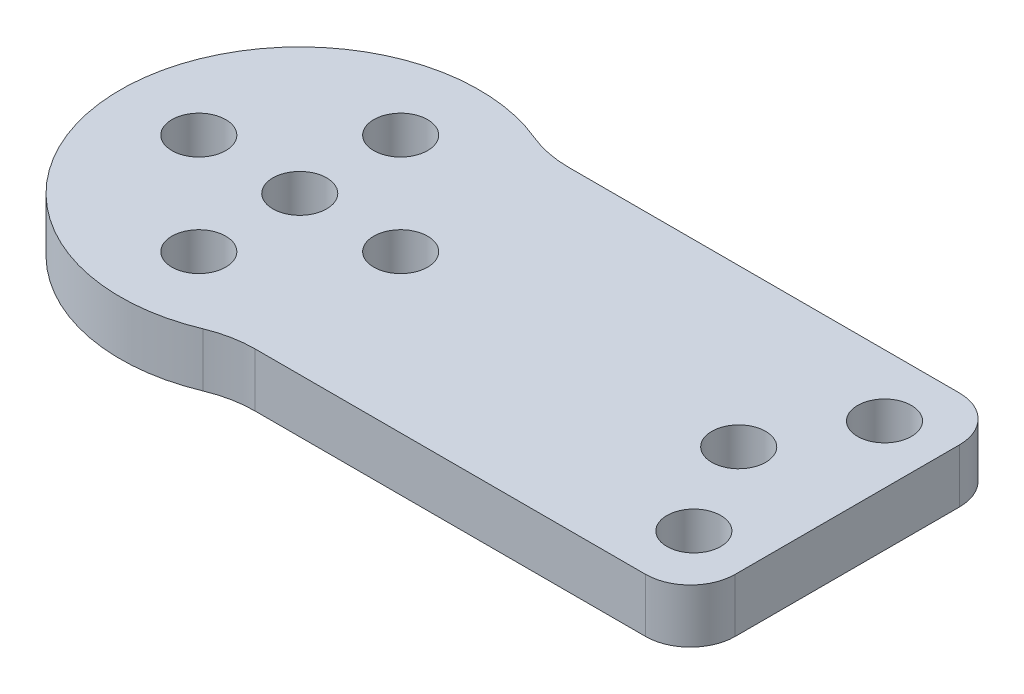
SolidWorks part; units mm, degrees
ref_plane "Front Plane" through (0, 0, 0) normal (0, 0, 1) x (1, 0, 0)
ref_plane "Top Plane" through (0, 0, 0) normal (0, 1, 0) x (1, 0, 0)
ref_plane "Right Plane" through (0, 0, 0) normal (1, 0, 0) x (0, 0, -1)
sketch "Sketch1" plane through (0, 0, 0) normal (0, 1, 0) x (1, 0, 0)
  line L0 (-12.7, 0) -> (12.7, 0) construction
  line L1 (-12.7, -7) -> (12.7, -7) construction
  line L2 (-12.7, 7) -> (12.7, 7) construction
  line L3 (11.7164, 7) -> (-8.827, 7)
  line L4 (-8.827, -7) -> (11.7164, -7)
  line L5 (11.7164, -7) -> (11.7164, 7)
  arc A0 (-8.827, 7) -> (-8.827, -7) centre (-12.7, 0) ccw
  circle A1 centre (-12.7, 0) radius 25.4 construction
  point P3 (0, 0)
  dimension "D1" = 50.8
  dimension "D2" = 16
  dimension "D3" = 7
  dimension "D4" = 7
extrude "Boss-Extrude1" add sketch "Sketch1" along normal mid plane 2.4
fillet "Fillet1" radius 2 2 edges at (11.7164, 0, -7) (11.7164, 0, 7)
fillet "Fillet2" radius 5 2 edges at (-8.827, 0, -7) (-8.827, 0, 7)
sketch "Sketch2" plane through (0, 1.2, 0) normal (0, 1, 0) x (1, 0, 0)
  circle A0 centre (-12.7, 0) radius 4.5 construction
  circle A1 centre (-8.2, 0) radius 1.2
  circle A2 centre (-12.7, 4.5) radius 1.2
  circle A3 centre (-17.2, 0) radius 1.2
  circle A4 centre (-12.7, -4.5) radius 1.2
  circle A5 centre (-12.7, 0) radius 1.2
  dimension "D1" = 2.4
  dimension "D2" = 9
extrude "Cut-Extrude1" cut sketch "Sketch2" against normal through all
sketch "Sketch3" plane through (0, 1.2, 0) normal (0, 1, 0) x (1, 0, 0)
  line L0 (9.1214, 4.25) -> (9.1214, -4.25) construction
  line L1 (9.1214, -4.25) -> (6.8714, 0) construction
  line L2 (6.8714, 0) -> (9.1214, 4.25) construction
  line L3 (11.7164, -5) -> (11.7164, 5) construction
  circle A0 centre (9.1214, 4.25) radius 1.2
  circle A1 centre (9.1214, -4.25) radius 1.2
  circle A2 centre (6.8714, 0) radius 1.2
  point P6 (0, 0)
  dimension "D1" = 2.4
  dimension "D2" = 2.25
  dimension "D3" = 4.25
  dimension "D4" = 2.595
extrude "Cut-Extrude2" cut sketch "Sketch3" against normal through all
equation "\"D4@Sketch3\"=(7.44-\"D2@Sketch3\")/2"
